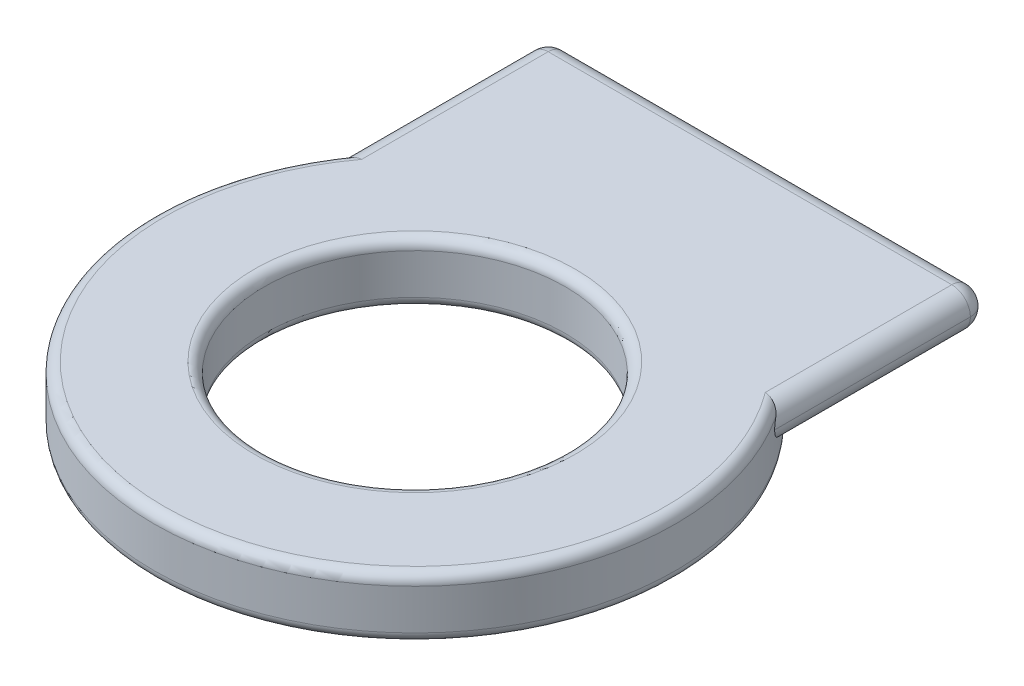
SolidWorks part; units mm, degrees
ref_plane "Front Plane" through (0, 0, 0) normal (0, 0, 1) x (1, 0, 0)
ref_plane "Top Plane" through (0, 0, 0) normal (0, 1, 0) x (1, 0, 0)
ref_plane "Right Plane" through (0, 0, 0) normal (1, 0, 0) x (0, 0, -1)
sketch "Sketch1" plane through (0, 0, 0) normal (0, 1, 0) x (1, 0, 0)
  line L1 (0, 0) -> (87.22, 0)
  line L2 (0, 0) -> (0, 70)
  line L3 (0, 70) -> (87.22, 70)
  line L4 (87.22, 0) -> (87.22, 70)
  dimension "D1" = 87.22
  dimension "D2" = 70
extrude "Boss-Extrude1" add sketch "Sketch1" along normal blind 7.35
sketch "Sketch2" plane through (0, 7.35, 0) normal (0, 1, 0) x (1, 0, 0)
  line L0 (0, 0) -> (87.22, 0) construction
  circle A0 centre (43.61, 0) radius 43.61
  dimension "D1" = 87.22
extrude "Boss-Extrude2" add sketch "Sketch2" against normal blind 12
sketch "Sketch3" plane through (0, 7.35, 0) normal (0, 1, 0) x (1, 0, 0)
  circle A0 centre (43.61, 0) radius 51.61
  arc A1 (0, 0) -> (87.22, 0) centre (43.61, 0) ccw construction
  dimension "D1" = 8
extrude "Boss-Extrude3" add sketch "Sketch3" against normal blind 12
sketch "Sketch4" plane through (0, 7.35, 0) normal (0, 1, 0) x (1, 0, 0)
  circle A0 centre (43.61, 0) radius 29.75
  dimension "D1" = 59.5
extrude "Cut-Extrude1" cut sketch "Sketch4" against normal blind 12
fillet "Fillet1" radius 3.675 4 edges at (87.22, 0, -48.8) (87.22, 7.35, -48.8) (0, 7.35, -48.8) (0, 0, -48.8)
fillet "Fillet2" radius 3.675 6 edges at (86.1436, 6.2736, -70) (86.1436, 1.0764, -70) (1.0764, 1.0764, -70) (1.0764, 6.2736, -70) (43.61, 0, -70) (43.61, 7.35, -70)
thread "Thread1" [suppressed] pitch 3 start angle 0, offset 0, length 10, pitch 3, diameter 66
ref_plane "Plane1" through (10.61, 7.35, 0) normal (0, 0, 1) x (-1, 0, 0)
sketch "Thread Profile1" plane through (10.61, 7.35, 0) normal (0, 0, 1) x (-1, 0, 0)
  line L0 (0, 0) -> (0, 3) construction
  line L11 (0, 0) -> (0, 2.625)
  line L12 (0, 2.625) -> (-1.6238, 1.6875)
  line L13 (-1.6238, 1.6875) -> (-1.6238, 0.9375)
  line L15 (-1.6238, 0.9375) -> (0, 0)
  line L17 (-1.6238, 1.3125) -> (0, 1.3125) construction
  point P2 (0, 0)
  dimension "Pitch" = 3
  dimension "Profile_Angle" = 60
  dimension "Profile_Land" = 0.75
  dimension "Profile_Height" = 1.6238
fillet "Fillet3" radius 2 3 edges at (43.61, -4.65, 51.61) (43.61, 7.35, 29.75) (43.61, 7.35, 51.61)
fillet "Fillet4" radius 2 1 edges at (43.61, -4.65, 29.75)
